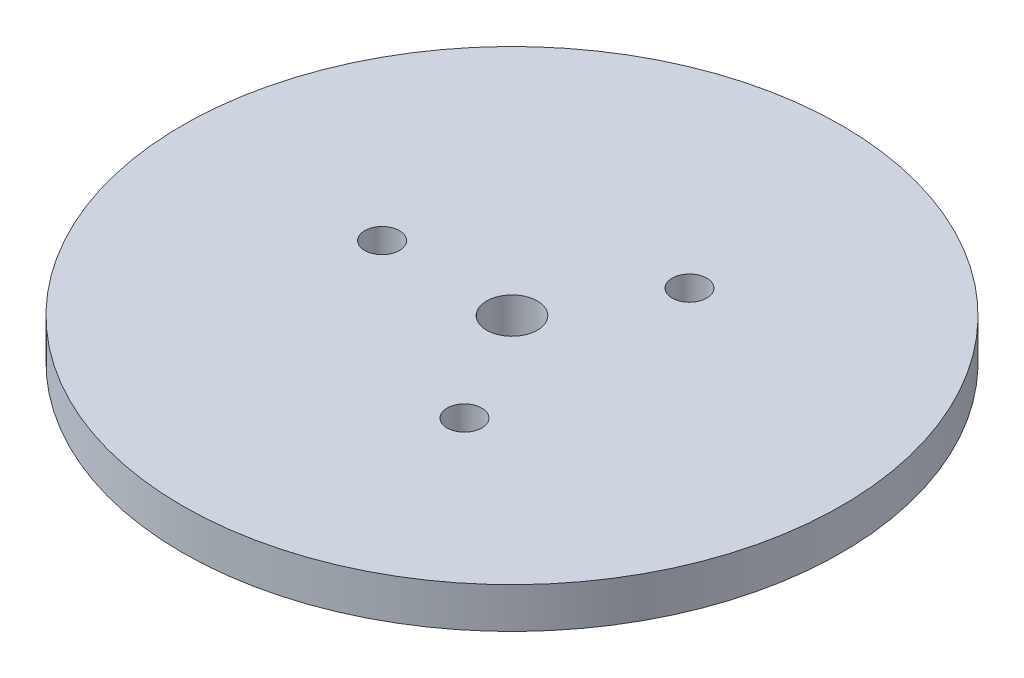
SolidWorks part; units mm, degrees
ref_plane "Front Plane" through (0, 0, 0) normal (0, 0, 1) x (1, 0, 0)
ref_plane "Top Plane" through (0, 0, 0) normal (0, 1, 0) x (1, 0, 0)
ref_plane "Right Plane" through (0, 0, 0) normal (1, 0, 0) x (0, 0, -1)
sketch "Sketch1" plane through (0, 0, 0) normal (0, 1, 0) x (1, 0, 0)
  circle A0 centre (0, 0) radius 65
  dimension "FLANGE_OD" = 130
extrude "Boss-Extrude1" add sketch "Sketch1" along normal blind 8
sketch "Sketch2" plane through (0, 0, 0) normal (0, 1, 0) x (1, 0, 0)
  circle A0 centre (0, 0) radius 5
  dimension "BORE_D" = 10
extrude "Cut-Extrude1" cut sketch "Sketch2" along normal through all
sketch "Sketch3" plane through (0, 8, 0) normal (0, 1, 0) x (1, 0, 0)
  circle A0 centre (0, 0) radius 25.6218 construction
  circle A1 centre (-25.6218, 0) radius 3.4165
  dimension "BOLT_D" = 6.833
  dimension "BOLT_PCD" = 51.2436
extrude "Cut-Extrude2" cut sketch "Sketch3" against normal blind 6.8591
pattern_circular "CirPattern1" count 3 over 360 about axis through (0, 0, 0) along (0, 1, 0) of "Cut-Extrude2"
